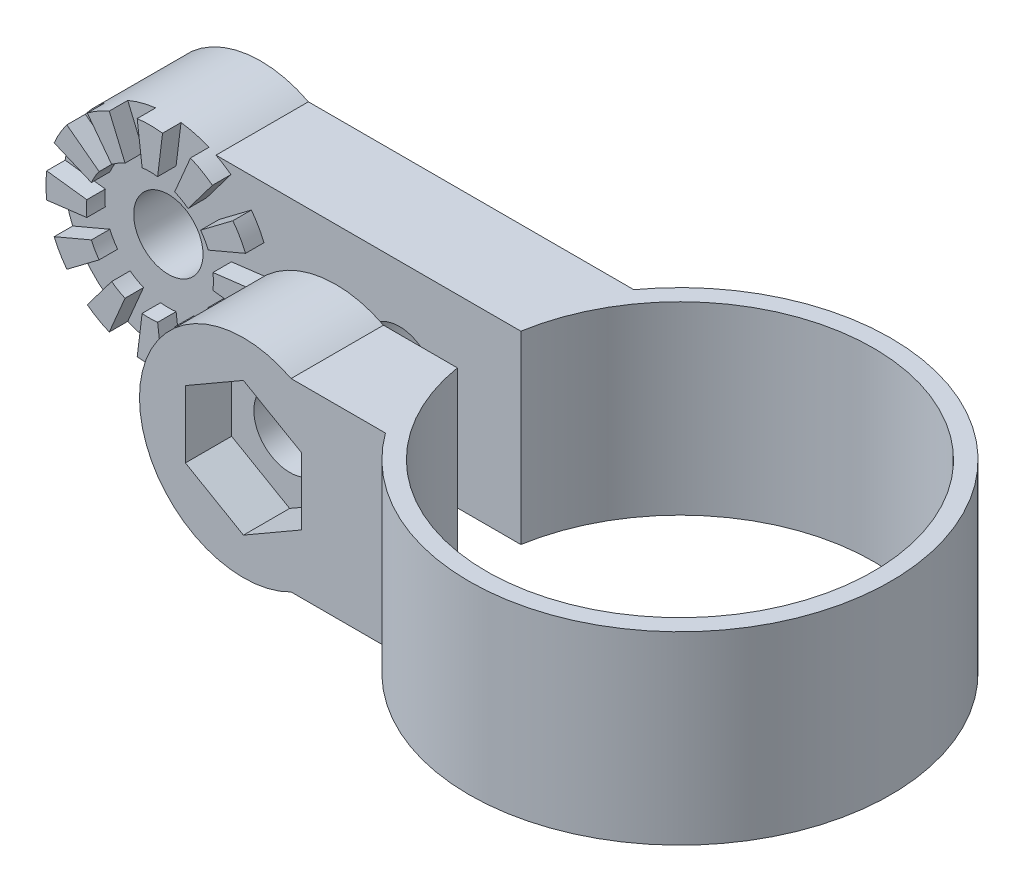
SolidWorks part; units mm, degrees
ref_plane "Alzado" through (0, 0, 0) normal (0, 0, 1) x (1, 0, 0)
ref_plane "Planta" through (0, 0, 0) normal (0, 1, 0) x (1, 0, 0)
ref_plane "Vista lateral" through (0, 0, 0) normal (1, 0, 0) x (0, 0, -1)
sketch "Croquis1" plane through (0, 0, 0) normal (0, 1, 0) x (1, 0, 0)
  line L0 (-18.0416, 2.75) -> (-18.0416, -2.75) construction
  line L1 (0, 0) -> (-41.7623, 0) construction
  line L2 (-18.0416, 2.75) -> (-56.0416, 2.75)
  line L5 (-14.7479, 10.75) -> (-56.0416, 10.75)
  line L6 (-56.0416, 10.75) -> (-56.0416, 2.75)
  line L7 (-18.0416, -2.75) -> (-36.0416, -2.75)
  line L8 (-14.7479, -10.75) -> (-36.0416, -10.75)
  line L9 (-36.0416, -2.75) -> (-36.0416, -10.75)
  line L10 (-18.0416, -2.75) -> (-16.5227, -2.75)
  line L11 (-18.0416, 2.75) -> (-16.5227, 2.75)
  arc A0 (-14.7479, -10.75) -> (-14.7479, 10.75) centre (0, 0) ccw
  arc A1 (-16.5227, -2.75) -> (-16.5227, 2.75) centre (0, 0) ccw
  point P6 (-18.0416, 0)
  dimension "D1" = 36.5
  dimension "D2" = 33.5
  dimension "D3" = 5.5
  dimension "D4" = 38
  dimension "D5" = 8
  dimension "D6" = 18
  dimension "D7" = 8
  dimension "D8" = 21.2937
  dimension "D9" = 1.5189
  dimension "D10" = 18.0416
extrude "Saliente-Extruir1" add sketch "Croquis1" along normal blind 16
sketch "Croquis2" plane through (0, 0, 10.75) normal (0, 0, 1) x (1, 0, 0)
  line L0 (-36.0416, 8) -> (-14.7479, 8) construction
  line L1 (-36.0416, 16) -> (-36.0416, 0) construction
  line L2 (-14.7479, 16) -> (-14.7479, 0) construction
  circle A0 centre (-27.0416, 8) radius 9
  circle A1 centre (-27.0416, 8) radius 3.1
  dimension "D1" = 9
  dimension "D2" = 6.2
  dimension "D3" = 18
extrude "Cortar-Extruir1" cut sketch "Croquis2" against normal blind 500 contours A1
sketch "Croquis3" plane through (0, 0, 10.75) normal (0, 0, 1) x (1, 0, 0)
  line L0 (-36.0416, 8) -> (-15.5151, 8) construction
  line L1 (-27.0416, 8) -> (-36.0416, 8) construction
  line L2 (-36.0416, 16) -> (-36.0416, 0) construction
  circle A0 centre (-27.0416, 8) radius 9
  circle A1 centre (-27.0416, 8) radius 3.1
  dimension "D2" = 6.2
  dimension "D3" = 18
  dimension "D1" = 9
extrude "Saliente-Extruir2" add sketch "Croquis3" against normal blind 8
sketch "Croquis5" plane through (0, 0, 10.75) normal (0, 0, 1) x (1, 0, 0)
  line L0 (-27.0416, 8) -> (-36.0416, 8) construction
  line L1 (-36.0416, 16) -> (-36.0416, 0) construction
  line L3 (-27.0416, 2.2) -> (-22.0187, 5.1)
  line L4 (-22.0187, 5.1) -> (-22.0187, 10.9)
  line L5 (-22.0187, 10.9) -> (-27.0416, 13.8)
  line L6 (-27.0416, 13.8) -> (-32.0646, 10.9)
  line L7 (-32.0646, 10.9) -> (-32.0646, 5.1)
  line L8 (-32.0646, 5.1) -> (-27.0416, 2.2)
  circle A0 centre (-27.0416, 8) radius 5.0229 construction
  dimension "D1" = 5.8
extrude "Cortar-Extruir2" cut sketch "Croquis5" against normal blind 4
sketch "Croquis7" plane through (0, 0, -2.75) normal (0, 0, 1) x (1, 0, 0)
  line L0 (-56.0416, 8) -> (-47.0416, 8) construction
  line L1 (-56.0416, 16) -> (-56.0416, 0) construction
  circle A0 centre (-47.0416, 8) radius 9
  dimension "D1" = 18
extrude "Saliente-Extruir3" add sketch "Croquis7" against normal blind 8
sketch "Croquis8" plane through (0, 0, -2.75) normal (0, 0, 1) x (1, 0, 0)
  line L0 (-56.0416, 8) -> (-47.0416, 8) construction
  line L1 (-56.0416, 16) -> (-56.0416, 0) construction
  line L2 (-47.0416, -1) -> (-47.0416, 17) construction
  line L3 (-47.0416, 8) -> (-43.5304, 36.5962) construction
  line L4 (-47.0416, 8) -> (-50.5528, 36.5962) construction
  line L5 (-47.7119, 13.459) -> (-48.1384, 16.9329)
  line L6 (-46.3713, 13.459) -> (-45.9448, 16.9329)
  line L7 (-43.7316, 12.3925) -> (-41.6253, 15.1877)
  line L8 (-44.8926, 13.0628) -> (-43.525, 16.2845)
  line L9 (-41.9788, 10.149) -> (-38.7571, 11.5166)
  line L10 (-42.6491, 11.31) -> (-39.8539, 13.4163)
  line L11 (-41.5826, 7.3297) -> (-38.1087, 6.9032)
  line L12 (-41.5826, 8.6703) -> (-38.1087, 9.0968)
  line L13 (-42.6491, 4.69) -> (-39.8539, 2.5837)
  line L14 (-41.9788, 5.851) -> (-38.7571, 4.4834)
  line L15 (-44.8926, 2.9372) -> (-43.525, -0.2845)
  line L16 (-43.7316, 3.6075) -> (-41.6253, 0.8123)
  line L17 (-47.7119, 2.541) -> (-48.1384, -0.9329)
  line L18 (-46.3713, 2.541) -> (-45.9448, -0.9329)
  line L19 (-50.3516, 3.6075) -> (-52.458, 0.8123)
  line L20 (-49.1906, 2.9372) -> (-50.5582, -0.2845)
  line L21 (-52.1044, 5.851) -> (-55.3262, 4.4834)
  line L22 (-51.4341, 4.69) -> (-54.2293, 2.5837)
  line L23 (-52.5006, 8.6703) -> (-55.9745, 9.0968)
  line L24 (-52.5006, 7.3297) -> (-55.9745, 6.9032)
  line L25 (-51.4341, 11.31) -> (-54.2293, 13.4163)
  line L26 (-52.1044, 10.149) -> (-55.3262, 11.5166)
  line L27 (-49.1906, 13.0628) -> (-50.5582, 16.2845)
  line L28 (-50.3516, 12.3925) -> (-52.458, 15.1877)
  line L31 (-16.5227, 16) -> (-16.5227, 0) construction
  line L32 (-42.9185, 0) -> (-16.5227, 0) construction
  circle A0 centre (-47.0416, 8) radius 9 construction
  circle A1 centre (-47.0416, 8) radius 3 construction
  circle A2 centre (-47.0416, 8) radius 5.5 construction
  arc A3 (-47.7119, 13.459) -> (-46.3713, 13.459) centre (-47.0416, 8) cw
  arc A4 (-48.1384, 16.9329) -> (-45.9448, 16.9329) centre (-47.0416, 8) cw
  arc A5 (-43.525, 16.2845) -> (-41.6253, 15.1877) centre (-47.0416, 8) cw
  arc A6 (-44.8926, 13.0628) -> (-43.7316, 12.3925) centre (-47.0416, 8) cw
  arc A7 (-39.8539, 13.4163) -> (-38.7571, 11.5166) centre (-47.0416, 8) cw
  arc A8 (-42.6491, 11.31) -> (-41.9788, 10.149) centre (-47.0416, 8) cw
  arc A9 (-38.1087, 9.0968) -> (-38.1087, 6.9032) centre (-47.0416, 8) cw
  arc A10 (-41.5826, 8.6703) -> (-41.5826, 7.3297) centre (-47.0416, 8) cw
  arc A11 (-38.7571, 4.4834) -> (-39.8539, 2.5837) centre (-47.0416, 8) cw
  arc A12 (-41.9788, 5.851) -> (-42.6491, 4.69) centre (-47.0416, 8) cw
  arc A13 (-41.6253, 0.8123) -> (-43.525, -0.2845) centre (-47.0416, 8) cw
  arc A14 (-43.7316, 3.6075) -> (-44.8926, 2.9372) centre (-47.0416, 8) cw
  arc A15 (-45.9448, -0.9329) -> (-48.1384, -0.9329) centre (-47.0416, 8) cw
  arc A16 (-46.3713, 2.541) -> (-47.7119, 2.541) centre (-47.0416, 8) cw
  arc A17 (-50.5582, -0.2845) -> (-52.458, 0.8123) centre (-47.0416, 8) cw
  arc A18 (-49.1906, 2.9372) -> (-50.3516, 3.6075) centre (-47.0416, 8) cw
  arc A19 (-54.2293, 2.5837) -> (-55.3262, 4.4834) centre (-47.0416, 8) cw
  arc A20 (-51.4341, 4.69) -> (-52.1044, 5.851) centre (-47.0416, 8) cw
  arc A21 (-55.9745, 6.9032) -> (-55.9745, 9.0968) centre (-47.0416, 8) cw
  arc A22 (-52.5006, 7.3297) -> (-52.5006, 8.6703) centre (-47.0416, 8) cw
  arc A23 (-55.3262, 11.5166) -> (-54.2293, 13.4163) centre (-47.0416, 8) cw
  arc A24 (-52.1044, 10.149) -> (-51.4341, 11.31) centre (-47.0416, 8) cw
  arc A25 (-52.458, 15.1877) -> (-50.5582, 16.2845) centre (-47.0416, 8) cw
  arc A26 (-50.3516, 12.3925) -> (-49.1906, 13.0628) centre (-47.0416, 8) cw
  point P62 (-47.0416, 8)
  dimension "D1" = 18
  dimension "D2" = 6
  dimension "D4" = 11
  dimension "D3" = 7
extrude "Saliente-Extruir4" add sketch "Croquis8" along normal mid plane 3.2
sketch "Croquis9" plane through (0, 0, -2.75) normal (0, 0, 1) x (1, 0, 0)
  circle A0 centre (-47.0416, 8) radius 3
  dimension "D1" = 6
extrude "Cortar-Extruir3" cut sketch "Croquis9" against normal blind 10
sketch "Croquis10" plane through (0, 0, -10.75) normal (0, 0, -1) x (-1, 0, 0)
  line L0 (47.0416, 8) -> (56.0416, 8) construction
  arc A0 (47.0416, 17) -> (47.0416, -1) centre (47.0416, 8) cw
  arc A1 (51.1647, 16) -> (42.9185, 16) centre (47.0416, 8) ccw construction
  arc A2 (42.9185, 0) -> (51.1647, 0) centre (47.0416, 8) ccw construction
  dimension "D1" = 9
extrude "Cortar-Extruir4" cut sketch "Croquis10" against normal blind 10 and the other way through all
sketch "Croquis11" plane through (0, 0, 10.75) normal (0, 0, 1) x (1, 0, 0)
  line L0 (-27.0416, 8) -> (-36.0416, 8) construction
  line L1 (-36.0416, 16) -> (-36.0416, 0) construction
  arc A0 (-27.0416, 17) -> (-27.0416, -1) centre (-27.0416, 8) ccw
  arc A1 (-22.9185, 16) -> (-31.1647, 16) centre (-27.0416, 8) ccw construction
  arc A2 (-31.1647, 0) -> (-22.9185, 0) centre (-27.0416, 8) ccw construction
  dimension "D1" = 9
extrude "Cortar-Extruir6" cut sketch "Croquis11" against normal blind 10 and the other way through all flip side to cut
